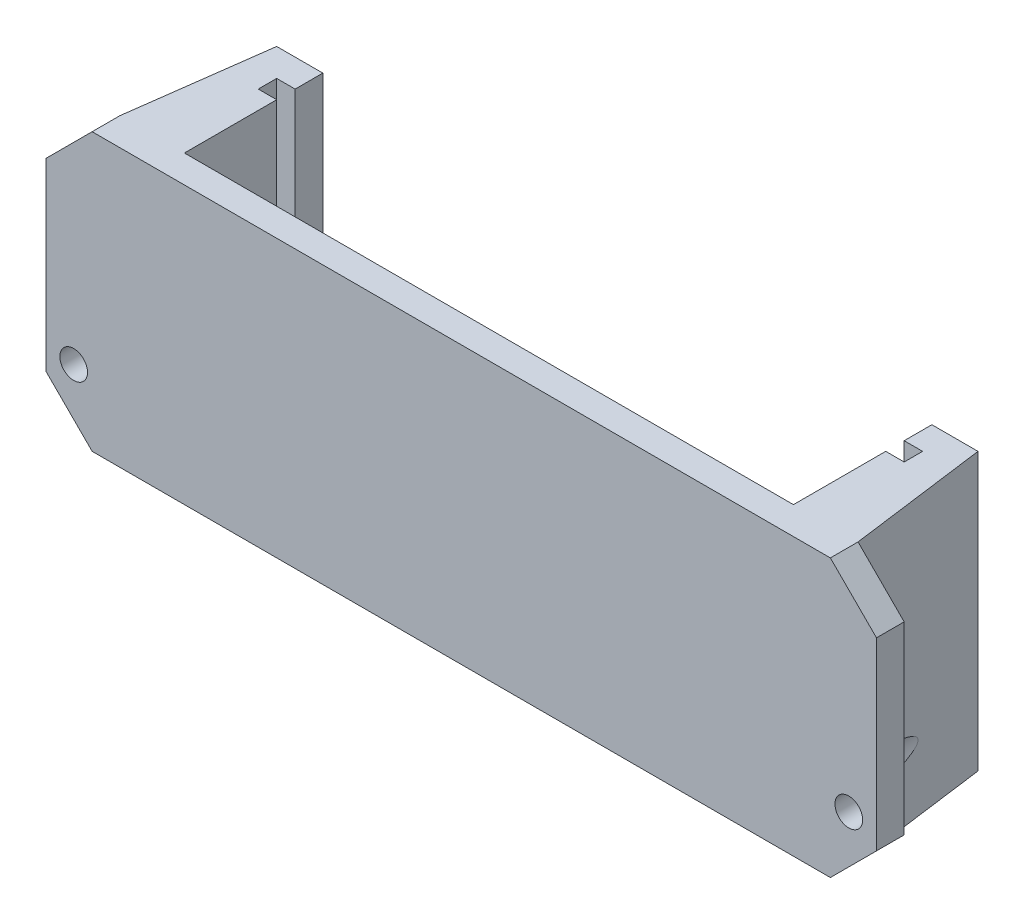
SolidWorks part; units mm, degrees
ref_plane "Front Plane" through (0, 0, 0) normal (0, 0, 1) x (1, 0, 0)
ref_plane "Top Plane" through (0, 0, 0) normal (0, 1, 0) x (1, 0, 0)
ref_plane "Right Plane" through (0, 0, 0) normal (1, 0, 0) x (0, 0, -1)
sketch "Sketch1" plane through (0, 0, 0) normal (0, 1, 0) x (1, 0, 0)
  line L0 (2, -3.1072) -> (2, 6.8928)
  line L1 (-10, -3.1072) -> (80, -3.1072)
  line L2 (-10, -3.1072) -> (-10, -6.1072)
  line L3 (-10, -6.1072) -> (80, -6.1072)
  line L4 (80, -3.1072) -> (80, -6.1072)
  line L5 (2, 6.8928) -> (0, 6.8928)
  line L6 (0, 6.8928) -> (0, 8.8928)
  line L7 (0, 8.8928) -> (2, 8.8928)
  line L8 (2, 8.8928) -> (2, 11.8928)
  line L9 (2, 11.8928) -> (-3, 11.8928)
  line L10 (-3, 11.8928) -> (-5, -3.1072)
  line L11 (68, -3.1072) -> (68, 6.8928)
  line L12 (68, 6.8928) -> (70, 6.8928)
  line L13 (70, 6.8928) -> (70, 8.8928)
  line L14 (70, 8.8928) -> (68, 8.8928)
  line L15 (68, 8.8928) -> (68, 11.8928)
  line L16 (68, 11.8928) -> (73, 11.8928)
  line L17 (73, 11.8928) -> (75, -3.1072)
  dimension "D1" = 3
  dimension "D2" = 90
  dimension "D3" = 2
  dimension "D4" = 2
  dimension "D5" = 10
  dimension "D6" = 3
  dimension "D7" = 7
  dimension "D8" = 70
  dimension "D9" = 5
  dimension "D10" = 12
extrude "Boss-Extrude1" add sketch "Sketch1" along normal blind 30 contours L4 L1 L2 L3 | L9 L10 L1 L0 L5 L6 L7 L8 | L17 L16 L15 L14 L13 L12 L11 L1 region at (-1.1221, 0, -3.794) region at (35, 0, 4.6072) region at (71.1221, 0, -3.794)
sketch "Sketch2" plane through (0, 0, 3.1072) normal (0, 0, -1) x (-1, 0, 0)
  line L0 (10, 30) -> (10, 0) construction
  circle A0 centre (7, 7.1547) radius 1.5
  circle A1 centre (-77, 7.1547) radius 1.5
  circle A2 centre (7, 7.1547) radius 3
  circle A3 centre (-77, 7.1547) radius 3
  dimension "D1" = 84
  dimension "D3" = 3
  dimension "D4" = 6
  dimension "D2" = 3
extrude "Cut-Extrude1" cut sketch "Sketch2" against normal blind 20 contours A0 | A1 region at (-7, 7.1547, 3.1072) region at (77, 7.1547, 3.1072)
extrude "Cut-Extrude2" cut sketch "Sketch2<3>" along normal blind 20
sketch "Sketch2<3>" plane through (0, 0, 3.1072) normal (0, 0, -1) x (-1, 0, 0) same geometry as "Sketch2"
chamfer "Chamfer1" distance 5 angle 45 4 edges at (80, 0, 4.6072) (80, 30, 4.6072) (-10, 0, 4.6072) (-10, 30, 4.6072)
